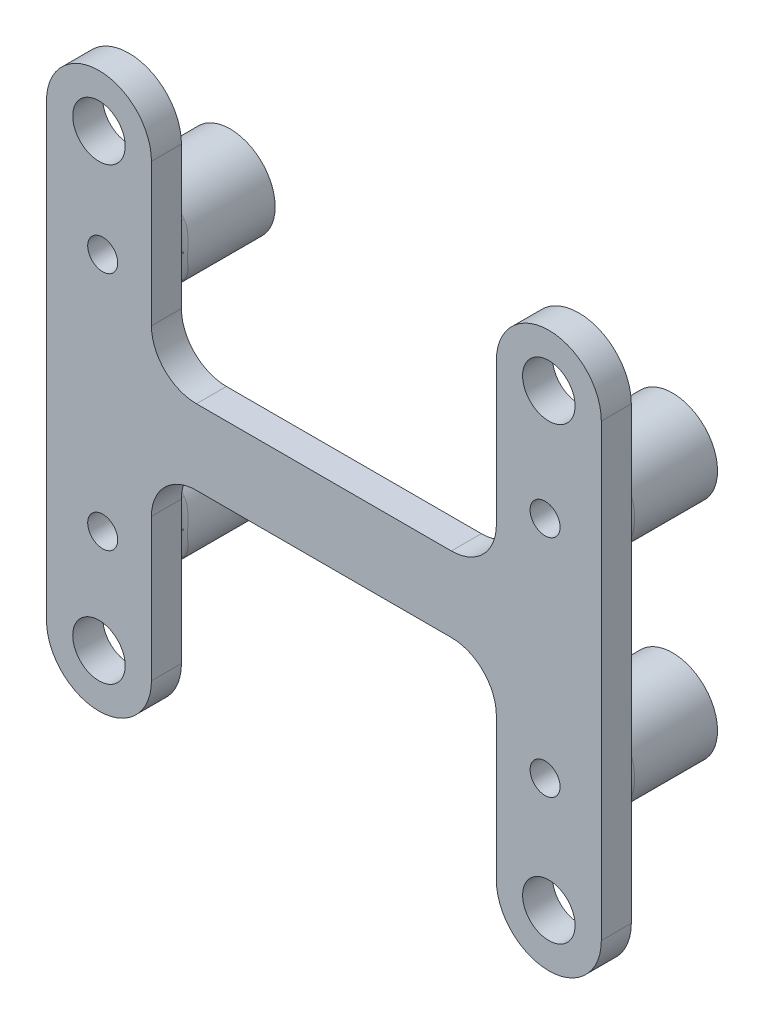
SolidWorks part; units mm, degrees
ref_plane "Спереди" through (0, 0, 0) normal (0, 0, 1) x (1, 0, 0)
ref_plane "Сверху" through (0, 0, 0) normal (0, 1, 0) x (1, 0, 0)
ref_plane "Справа" through (0, 0, 0) normal (1, 0, 0) x (0, 0, -1)
sketch "Эскиз1" plane through (0, 0, 0) normal (0, 0, 1) x (1, 0, 0)
  line L5 (11.0242, 11) -> (11.0242, 2.5)
  line L6 (-15.2258, 8) -> (-15.2258, -8) construction
  line L7 (11.0242, -11) -> (18.0242, -11)
  line L8 (14.2742, 7.5) -> (14.2742, -7.5) construction
  line L9 (-15.2258, 8) -> (14.2742, -7.5) construction
  line L10 (-15.2258, -8) -> (14.2742, 7.5) construction
  line L11 (18.0242, 11) -> (18.0242, -11)
  line L12 (-18.9758, 11) -> (-18.9758, -11)
  line L13 (18.0242, 11) -> (11.0242, 11)
  line L23 (-18.9758, 11) -> (-11.9758, 11)
  line L24 (-11.9758, 11) -> (-11.9758, 2.5)
  line L25 (-11.9758, -11) -> (-18.9758, -11)
  line L26 (11.0242, 2.5) -> (-11.9758, 2.5)
  line L27 (11.0242, -2.5) -> (-11.9758, -2.5)
  line L28 (11.0242, -2.5) -> (11.0242, -11)
  line L29 (-11.9758, -2.5) -> (-11.9758, -11)
  line L30 (-11.9758, 2.5) -> (-11.9758, -2.5) construction
  circle A8 centre (14.2742, 7.5) radius 1
  circle A9 centre (-15.2258, -8) radius 1
  circle A10 centre (14.2742, -7.5) radius 1
  circle A11 centre (-15.2258, 8) radius 1
  point P4 (0, 0)
  point P18 (-11.9758, 0)
  point P20 (-15.2258, 0)
  point P28 (0, 0)
  point P42 (-18.9758, 0)
  dimension "D3" = 16
  dimension "D4" = 2
  dimension "D7" = 3.5
  dimension "D8" = 3.75
  dimension "D1" = 5
  dimension "D2" = 29.5
  dimension "D5" = 15
  dimension "D6" = 7
  dimension "D9" = 3.75
extrude "Основа" add sketch "Эскиз1" against normal blind 2 contours L29 L27 L28 L7 L11 L13 L5 L26 L24 L23 L12 L25 A11 A10 A9 A8 region at (-0.4758, 0, 0)
sketch "Эскиз6" plane through (0, 0, -2) normal (0, 0, -1) x (-1, 0, 0)
  circle A0 centre (-14.2742, 7.5) radius 3
  circle A1 centre (-14.2742, -7.5) radius 3
  circle A2 centre (15.2258, 8) radius 3
  circle A3 centre (15.2258, -8) radius 3
  circle A4 centre (-14.2742, 7.5) radius 1
  circle A5 centre (-14.2742, -7.5) radius 1
  circle A6 centre (15.2258, 8) radius 1
  circle A7 centre (15.2258, -8) radius 1
  circle A8 centre (-14.2742, 7.5) radius 1 construction
  dimension "D1" = 6
extrude "Стойки для крепления датчика" add sketch "Эскиз6" along normal blind 6.5
sketch "Эскиз7" plane through (0, 0, 0) normal (0, 0, 1) x (1, 0, 0)
  line L0 (-18.9758, 15) -> (-18.9758, 11)
  line L1 (-18.9758, 11) -> (-11.9758, 11) construction
  line L2 (-18.9758, 11) -> (-11.9758, 11)
  line L3 (-11.9758, 11) -> (-11.9758, 15)
  line L4 (-0.4758, 2.5) -> (-0.4758, 0) construction
  line L6 (-0.4758, 0) -> (18.0242, 0) construction
  line L7 (18.0242, 11) -> (18.0242, -11) construction
  line L8 (11.0242, 11) -> (11.0242, 15)
  line L9 (18.0242, 11) -> (11.0242, 11)
  line L10 (18.0242, 15) -> (18.0242, 11)
  line L11 (18.0242, -15) -> (18.0242, -11)
  line L12 (18.0242, -11) -> (11.0242, -11)
  line L13 (11.0242, -11) -> (11.0242, -15)
  line L14 (-11.9758, -11) -> (-11.9758, -15)
  line L15 (-18.9758, -11) -> (-11.9758, -11)
  line L16 (-18.9758, -15) -> (-18.9758, -11)
  line L17 (11.0242, 2.5) -> (-11.9758, 2.5) construction
  circle A0 centre (-15.4758, 15) radius 1.75
  arc A1 (-11.9758, 15) -> (-18.9758, 15) centre (-15.4758, 15) ccw
  arc A2 (11.0242, 15) -> (18.0242, 15) centre (14.5242, 15) cw
  circle A3 centre (14.5242, 15) radius 1.75
  circle A4 centre (14.5242, -15) radius 1.75
  arc A5 (11.0242, -15) -> (18.0242, -15) centre (14.5242, -15) ccw
  arc A6 (-11.9758, -15) -> (-18.9758, -15) centre (-15.4758, -15) cw
  circle A7 centre (-15.4758, -15) radius 1.75
  dimension "D1" = 30
  dimension "D3" = 3.5
  dimension "D4" = 3.5
  dimension "D2" = 30
extrude "Крепежные уши 4 штуки" add sketch "Эскиз7" against normal blind 2
sketch "Эскиз8" [suppressed] plane through (0, 0, -2) normal (0, 0, -1) x (-1, 0, 0)
  line L0 (-24.5, 3.5) -> (-18, 3.5)
  line L1 (-18, 4.8542) -> (-18, -4.8542) construction
  line L2 (-18, 3.5) -> (-18, -3.5)
  line L3 (-18, -3.5) -> (-24.5, -3.5)
  line L4 (0.5, 2.5) -> (0.5, -2.5) construction
  line L5 (-11, 2.5) -> (12, 2.5) construction
  line L6 (-11, -2.5) -> (12, -2.5) construction
  line L7 (19, -3.5) -> (25.5, -3.5)
  line L8 (19, 3.5) -> (19, -3.5)
  line L9 (25.5, 3.5) -> (19, 3.5)
  circle A0 centre (-24.5, 0) radius 1.75
  arc A1 (-24.5, 3.5) -> (-24.5, -3.5) centre (-24.5, 0) ccw
  arc A2 (25.5, 3.5) -> (25.5, -3.5) centre (25.5, 0) cw
  circle A3 centre (25.5, 0) radius 1.75
  dimension "D1" = 50
  dimension "D2" = 3.5
  dimension "D3" = 3.5
extrude "Боковые уши" [suppressed] add sketch "Эскиз8" against normal blind 2
fillet "Скругление7" radius 3 4 edges at (11.0242, 2.5, -1) (-11.9758, 2.5, -1) (-11.9758, -2.5, -1) (11.0242, -2.5, -1)
fillet "Скругление4" radius 1 4 edges at (-18.2258, -8, -2) (-18.2258, 8, -2) (17.2742, -7.5, -2) (17.2742, 7.5, -2)
